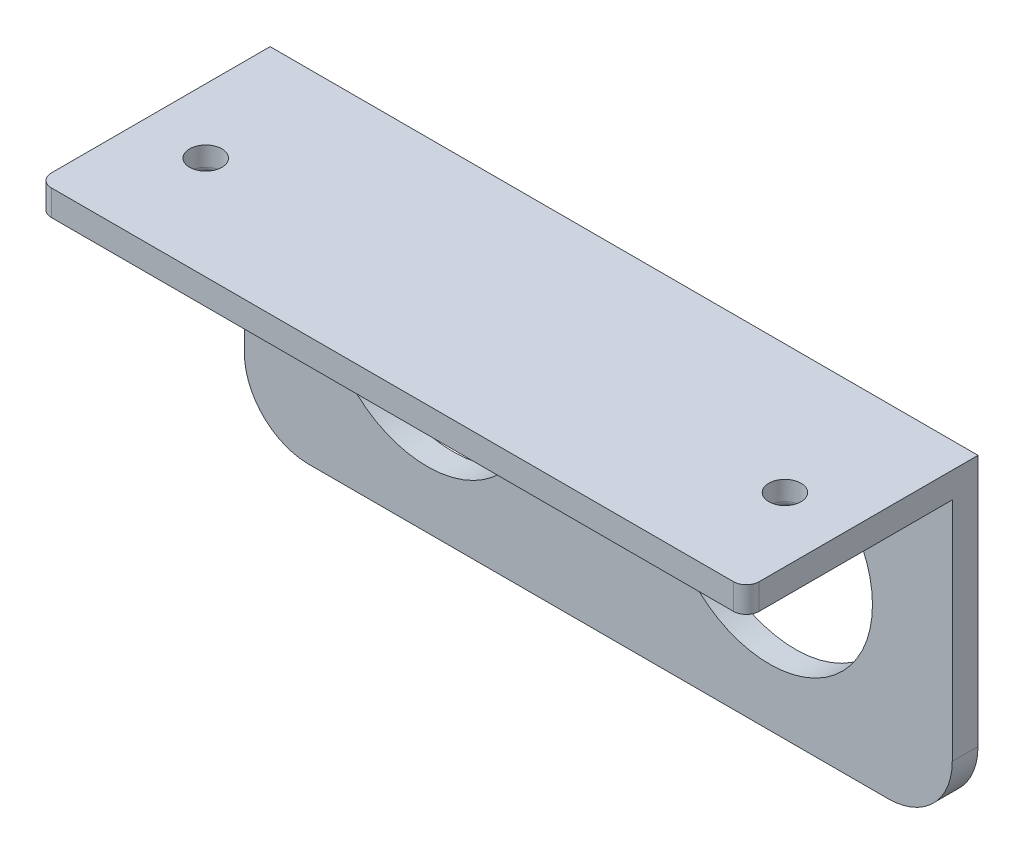
SolidWorks part; units mm, degrees
other "Markup1"
sketch "Sketch7" plane through (-20.0719, -0.3318, 12) normal (-0.8831, -0.2604, 0.3903) x (-0.3657, -0.1393, -0.9203)
other "Markup2"
sketch "Sketch23" plane through (-28.5719, 1.0682, 18) normal (-0.0368, -0.1105, 0.9932) x (-0.9991, 0.0251, -0.0342)
other "Markup3"
sketch "Sketch24" plane through (-28.5719, 1.0682, 18) normal (-0.0368, -0.1105, 0.9932) x (-0.9991, 0.0251, -0.0342)
ref_plane "Front Plane" through (0, 0, 0) normal (0, 0, 1) x (1, 0, 0)
ref_plane "Top Plane" through (0, 0, 0) normal (0, 1, 0) x (1, 0, 0)
ref_plane "Right Plane" through (0, 0, 0) normal (1, 0, 0) x (0, 0, -1)
sketch "Sketch1" plane through (0, 0, 0) normal (0, 0, 1) x (1, 0, 0)
  line L1 (-28.5719, 23.6682) -> (26.4281, 23.6682)
  line L2 (-28.5719, 23.6682) -> (-28.5719, 1.0682)
  line L3 (-28.5719, 1.0682) -> (26.4281, 1.0682)
  line L4 (26.4281, 23.6682) -> (26.4281, 1.0682)
  dimension "D1" = 55
  dimension "D2" = 22.6
extrude "Boss-Extrude1" add sketch "Sketch1" along normal blind 2 contours L1 L4 L3 L2
sketch "Sketch2" plane through (0, 0, 2) normal (0, 0, 1) x (1, 0, 0)
  line L1 (-28.5719, 23.6682) -> (26.4281, 23.6682) construction
  line L4 (-28.5719, 23.6682) -> (-28.5719, 1.0682) construction
  circle A0 centre (-14.3719, 13.5182) radius 8
  circle A1 centre (12.2281, 13.5182) radius 8
  dimension "D5" = 16
  dimension "D6" = 16
  dimension "D1" = 26.6
  dimension "D2" = 10.15
  dimension "D3" = 14.2
  dimension "D4" = 10.15
extrude "Cut-Extrude2" cut sketch "Sketch2" against normal blind 2 contours A0
extrude "Cut-Extrude3" cut sketch "Sketch2<4>" against normal blind 2
sketch "Sketch2<4>" plane through (0, 0, 2) normal (0, 0, 1) x (1, 0, 0) same geometry as "Sketch2"
sketch "Sketch5" plane through (0, 0, 2) normal (0, 0, 1) x (1, 0, 0)
  line L0 (-28.5719, 23.6682) -> (26.4281, 23.6682) construction
  line L1 (-6.1719, 23.6682) -> (3.8281, 23.6682)
  line L2 (-6.1719, 23.6682) -> (-6.1719, 18.9682)
  line L3 (-6.1719, 18.9682) -> (3.8281, 18.9682)
  line L4 (3.8281, 23.6682) -> (3.8281, 18.9682)
  line L5 (-28.5719, 23.6682) -> (-28.5719, 1.0682) construction
  dimension "D1" = 4.7
  dimension "D2" = 10
  dimension "D3" = 22.4
extrude "Cut-Extrude4" cut sketch "Sketch5" against normal blind 2 contours L3 L4 L1 L2
sketch "Sketch6" plane through (0, 0, 0) normal (0, 0, -1) x (-1, 0, 0)
  line L1 (28.5719, 25.6682) -> (-26.4281, 25.6682)
  line L2 (28.5719, 25.6682) -> (28.5719, 23.6682)
  line L3 (28.5719, 23.6682) -> (-26.4281, 23.6682)
  line L4 (-26.4281, 25.6682) -> (-26.4281, 23.6682)
  dimension "D1" = 55
  dimension "D2" = 2
extrude "Boss-Extrude2" add sketch "Sketch6" against normal blind 18 contours L1 L4 L3 L2
sketch "Sketch18" plane through (0, 23.6682, 0) normal (0, -1, 0) x (-1, 0, 0)
  line L0 (23.5719, -10) -> (-21.4281, -10)
  line L1 (-26.4281, -18) -> (-26.4281, -2) construction
  line L2 (28.5719, -18) -> (28.5719, -2) construction
  point P3 (1.0719, -10)
  dimension "D1" = 45
  dimension "D2" = 5
  dimension "D3" = 5
hole_wizard "M3x0.5 Tapped Hole1" positions "Sketch19" profile "Sketch20" tap size "M3x0.5" standard "ANSI Metric" end condition through all
sketch "Sketch19" plane through (0, 23.6682, 0) normal (0, -1, 0) x (-1, 0, 0)
  point P0 (-21.4281, -10)
sketch "Sketch20" plane through (21.4281, 23.6682, 10) normal (1, 0, 0) x (0, 0, -1)
  line L0 (0, 0) -> (0, 2)
  line L1 (0, 2) -> (1.25, 2)
  line L2 (1.25, 2) -> (1.25, 0)
  line L5 (1.25, 0) -> (0, 0)
  line L11 (0, -6.35) -> (0, 107.95) construction
  dimension "Thru Tap Drill Dia." = 2.5
  dimension "Thru Tap Drill Depth" = 2
cosmetic thread "Hole Thread1" parameters "D2"=3
hole_wizard "M3x0.5 Tapped Hole2" positions "Sketch21" profile "Sketch22" tap size "M3x0.5" standard "ANSI Metric" end condition through all
sketch "Sketch21" plane through (0, 23.6682, 0) normal (0, -1, 0) x (-1, 0, 0)
  point P0 (23.5719, -10)
sketch "Sketch22" plane through (-23.5719, 23.6682, 10) normal (1, 0, 0) x (0, 0, -1)
  line L0 (0, 0) -> (0, 2)
  line L1 (0, 2) -> (1.25, 2)
  line L2 (1.25, 2) -> (1.25, 0)
  line L5 (1.25, 0) -> (0, 0)
  line L11 (0, -6.35) -> (0, 107.95) construction
  dimension "Thru Tap Drill Dia." = 2.5
  dimension "Thru Tap Drill Depth" = 2
cosmetic thread "Hole Thread2" parameters "D2"=3
fillet "Fillet1" radius 5 1 edges at (-28.5719, 1.0682, 1) type face fillet first side face at (-1.0719, 1.0682, 1) second side face at (-28.5719, 16.8015, 6.6667)
fillet "Fillet2" radius 5 1 edges at (26.4281, 1.0682, 1) type face fillet first side face at (1.4281, 1.0682, 1) second side face at (26.4281, 16.8015, 6.6667)
fillet "Fillet4" radius 1.8 1 edges at (3.8281, 18.9682, 1)
fillet "Fillet5" radius 1.8 1 edges at (-6.1719, 18.9682, 1)
fillet "Fillet10" radius 1 2 edges at (26.4281, 24.6682, 18) (-28.5719, 24.6682, 18)
fillet "Fillet12" radius 0.5 1 edges at (-23.5719, 23.6682, 8.75)
fillet "Fillet13" radius 0.5 1 edges at (21.4281, 23.6682, 8.75)
sketch "Sketch25" plane through (0, 23.6682, 0) normal (0, -1, 0) x (1, 0, 0)
sketch "Sketch26" plane through (0, 23.6682, 0) normal (0, -1, 0) x (1, 0, 0)
